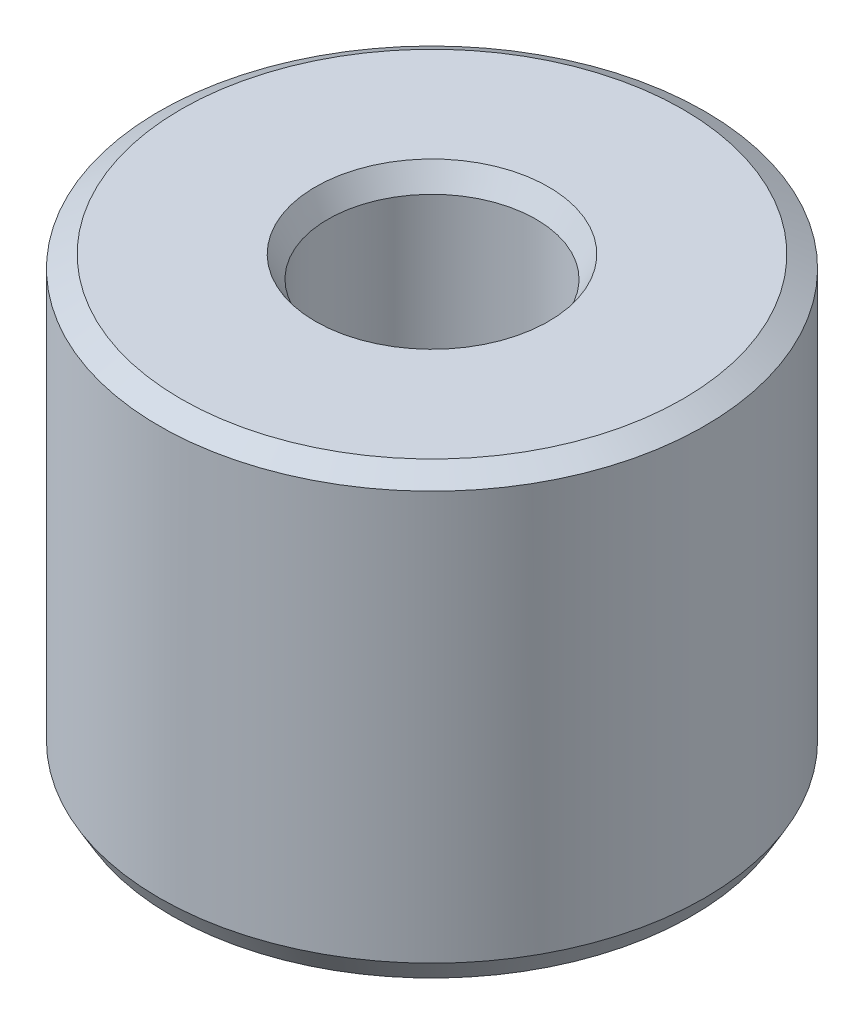
SolidWorks part; units mm, degrees
ref_plane "Front Plane" through (0, 0, 0) normal (0, 0, 1) x (1, 0, 0)
ref_plane "Top Plane" through (0, 0, 0) normal (0, 1, 0) x (1, 0, 0)
ref_plane "Right Plane" through (0, 0, 0) normal (1, 0, 0) x (0, 0, -1)
sketch "Sketch1" plane through (0, 0, 0) normal (0, 1, 0) x (1, 0, 0)
  circle A0 centre (0, 0) radius 30
  dimension "SLEEVE_OD" = 60
extrude "Boss-Extrude1" add sketch "Sketch1" along normal blind 48.7459
sketch "Sketch2" plane through (0, 0, 0) normal (0, 1, 0) x (1, 0, 0)
  circle A0 centre (0, 0) radius 11.4453
  dimension "BORE_D" = 22.8906
extrude "Cut-Extrude1" cut sketch "Sketch2" along normal through all
chamfer "Chamfer1" distance 1.38 angle 60 4 edges at (0, 48.7459, 11.4453) (0, 0, 11.4453) (0, 0, 30) (0, 48.7459, 30) first distance on face at (0, 48.7459, 11.4453) first distance on face at (0, 0, 11.4453) first distance on face at (0, 48.7459, 30)
